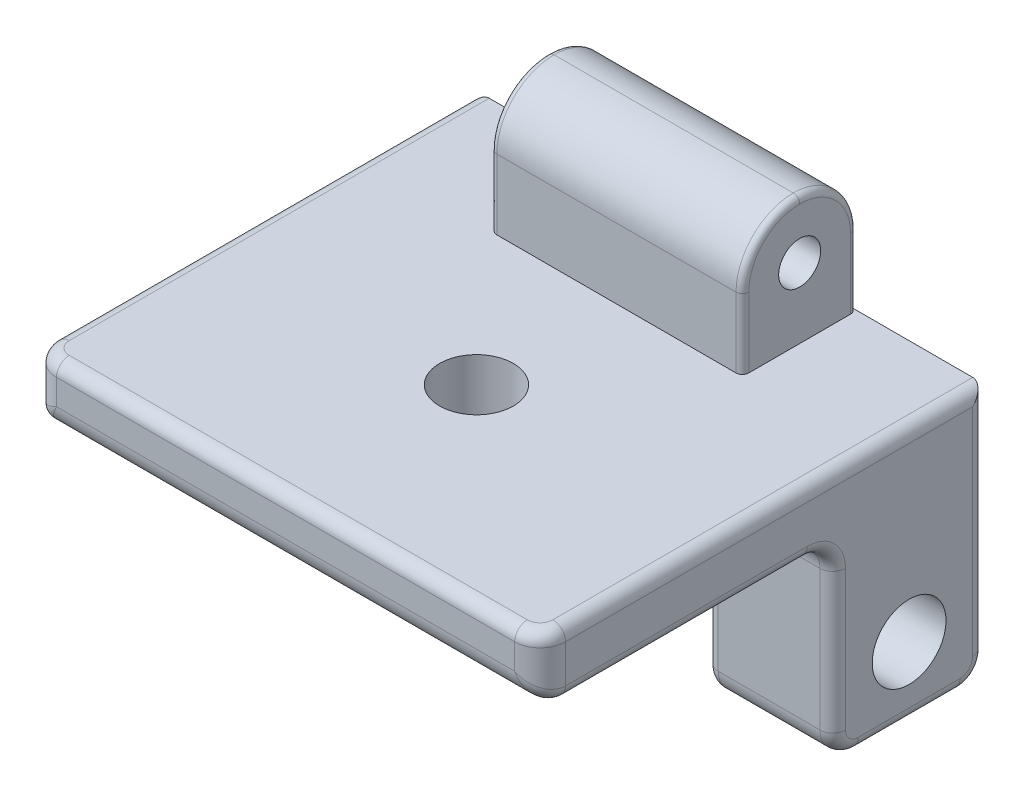
SolidWorks part; units mm, degrees
ref_plane "Front Plane" through (0, 0, 0) normal (0, 0, 1) x (1, 0, 0)
ref_plane "Top Plane" through (0, 0, 0) normal (0, 1, 0) x (1, 0, 0)
ref_plane "Right Plane" through (0, 0, 0) normal (1, 0, 0) x (0, 0, -1)
sketch "Sketch1" plane through (0, 0, 0) normal (0, 1, 0) x (1, 0, 0)
  line L1 (-20, -17.5) -> (20, -17.5)
  line L2 (-20, -17.5) -> (-20, 17.5)
  line L3 (-20, 17.5) -> (20, 17.5)
  line L4 (20, -17.5) -> (20, 17.5)
  line L5 (-20, -17.5) -> (20, 17.5) construction
  line L6 (-20, 17.5) -> (20, -17.5) construction
  circle A0 centre (0, -2.5) radius 2.9
  point P0 (0, 0)
  point P8 (0, 0)
  dimension "D4" = 5.8
  dimension "D1" = 35
  dimension "D2" = 40
  dimension "D3" = 15
extrude "Boss-Extrude1" add sketch "Sketch1" along normal blind 5
sketch "Sketch2" plane through (0, 5, 0) normal (0, 1, 0) x (1, 0, 0)
  line L0 (20, 17.5) -> (-20, 17.5) construction
  line L1 (-9.9, 17.5) -> (9.9, 17.5)
  line L2 (-9.9, 17.5) -> (-9.9, 8.5)
  line L3 (-9.9, 8.5) -> (9.9, 8.5)
  line L4 (9.9, 17.5) -> (9.9, 8.5)
  point P6 (0, 17.5)
  point P7 (0, 17.5)
  dimension "D1" = 19.8
  dimension "D2" = 9
extrude "Boss-Extrude2" add sketch "Sketch2" along normal blind 10
sketch "Sketch3" plane through (9.9, 0, 0) normal (1, 0, 0) x (0, 0, -1)
  line L0 (8.5, 15) -> (17.5, 15) construction
  line L1 (8.5, 5) -> (17.5, 5) construction
  circle A0 centre (13, 10.5) radius 1.65
  point P2 (0, 0)
  point P5 (13, 15)
  dimension "D1" = 3.3
  dimension "D2" = 5.5
extrude "Cut-Extrude1" cut sketch "Sketch3" against normal up to next
sketch "Sketch5" plane through (-20, 0, 0) normal (-1, 0, 0) x (0, 0, 1)
  line L0 (-17.5, 0) -> (-17.5, -15)
  line L1 (-17.5, -15) -> (-5.5, -15)
  line L2 (-5.5, -15) -> (-5.5, 0)
  line L3 (-17.5, 0) -> (17.5, 0) construction
  line L4 (-5.5, 0) -> (-17.5, 0)
  circle A0 centre (-11.5, -9.5) radius 2.15
  point P8 (-17.5, -15)
  point P11 (0, 0)
  point P12 (-6.5, -15)
  point P13 (-16.5, -15)
  point P14 (0, 0)
  point P15 (-11.5, -15)
  dimension "D4" = 4.3
  dimension "D1" = 12
  dimension "D2" = 12
  dimension "D3" = 15
  dimension "D5" = 5.5
extrude "Boss-Extrude3" add sketch "Sketch5" against normal blind 10
mirror "Mirror1" about plane through (0, 0, 0) normal (1, 0, 0) of "Boss-Extrude3"
sketch "Sketch6" plane through (20, 0, 0) normal (1, 0, 0) x (0, 0, -1)
  circle A0 centre (11.5, -9.5) radius 2.9
  dimension "D1" = 5.8
extrude "Cut-Extrude2" cut sketch "Sketch6" against normal up to next
fillet "Fillet1" radius 2 4 edges at (-15, -15, -5.5) (-15, -15, -17.5) (15, -15, -5.5) (15, -15, -17.5)
fillet "Fillet3" radius 4.5 2 edges at (0, 15, -8.5) (0, 15, -17.5)
fillet "Fillet4" radius 0.5 8 edges at (9.9, 7.75, -8.5) (9.9, 13.682, -9.818) (9.9, 13.682, -16.182) (-9.9, 7.75, -8.5) (-9.9, 13.682, -9.818) (-9.9, 7.75, -17.5) (9.9, 7.75, -17.5) (-9.9, 13.682, -16.182)
fillet "Fillet5" radius 2 5 edges at (15, 0, -5.5) (-15, 0, -5.5) (0, 0, 17.5) (20, 2.5, 17.5) (-20, 2.5, 17.5)
fillet "Fillet6" radius 1 33 edges at (20, 5, -1) (19.4142, 5, 16.9142) (0, 5, 17.5) (-19.4142, 5, 16.9142) (19.4142, 0.5858, 16.9142) (20, -4, -17.5) (20, -14.4142, -16.9142) (20, -15, -11.5) (20, -14.4142, -6.0858) (20, -7.5, -5.5) (20, -0.5858, -4.9142) (-20, -4, -17.5) (-20, -14.4142, -16.9142) (-20, -15, -11.5) (-20, -14.4142, -6.0858) (-20, -7.5, -5.5) (-20, -0.5858, -4.9142) (-19.4142, 0.5858, 16.9142) (-20, 5, -1) (20, 0, 6) (-20, 0, 6) (10, -6.5, -17.5) (10, -14.4142, -16.9142) (10, -15, -11.5) (10, -14.4142, -6.0858) (10, -0.5858, -4.9142) (-10, -6.5, -17.5) (-10, -14.4142, -16.9142) (-10, -15, -11.5) (-10, -14.4142, -6.0858) (-10, -0.5858, -4.9142) (10, -7.5, -5.5) (-10, -7.5, -5.5)
